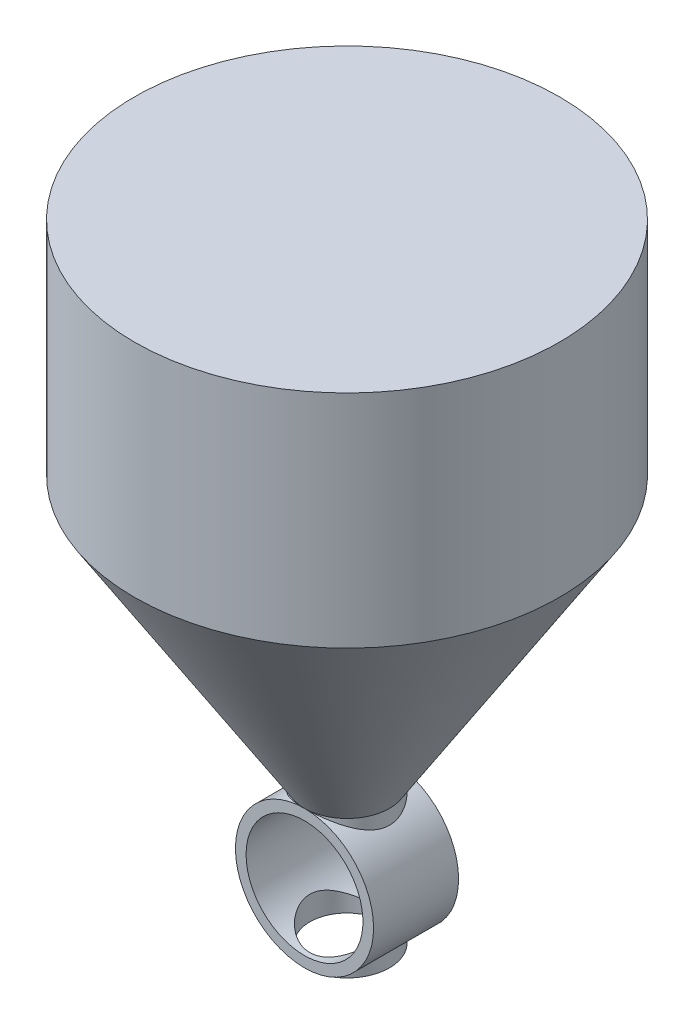
SolidWorks part; units mm, degrees
ref_plane "Alzado" through (0, 0, 0) normal (0, 0, 1) x (1, 0, 0)
ref_plane "Planta" through (0, 0, 0) normal (0, 1, 0) x (1, 0, 0)
ref_plane "Vista lateral" through (0, 0, 0) normal (1, 0, 0) x (0, 0, -1)
sketch "Croquis1" plane through (0, 0, 0) normal (0, 1, 0) x (1, 0, 0)
  circle A0 centre (0, 0) radius 100
  dimension "D1" = 200
ref_plane "Plano1" through (0, -230, 0) normal (0, 1, 0) x (1, 0, 0)
extrude "Saliente-Extruir1" add sketch "Croquis1" against normal blind 104 contours A0
sketch "Croquis2" plane through (0, -104, 0) normal (0, -1, 0) x (1, 0, 0)
  circle A2 centre (0, 0) radius 100
sketch "Croquis3" plane through (0, -230, 0) normal (0, 1, 0) x (1, 0, 0)
  circle A0 centre (0, 0) radius 20
  dimension "D1" = 40
loft "Recubrir1" add profiles "Croquis3", "Croquis2" connector at (-19.9701, -230, 1.0927) connector at (-99.8027, -104, 6.2791)
sketch "Croquis4" plane through (0, -230, 0) normal (0, -1, 0) x (1, 0, 0)
  circle A0 centre (0, 0) radius 20
  dimension "D1" = 40
extrude "Saliente-Extruir2" add sketch "Croquis4" along normal blind 65
ref_plane "Plano2" through (0, 0, -20) normal (0, 0, -1) x (-1, 0, 0)
sketch "Croquis5" plane through (0, 0, -20) normal (0, 0, -1) x (-1, 0, 0)
  line L0 (0, -230) -> (0, -295) construction
  line L1 (110, -230) -> (-110, -230) construction
  line L2 (-32.5, -262.5) -> (32.5, -262.5) construction
  circle A0 centre (0, -262.5) radius 32.5
  point P7 (0, -262.5)
  point P8 (0, -262.5)
  dimension "D1" = 65
  dimension "D2" = 65
extrude "Saliente-Extruir3" add sketch "Croquis5" against normal blind 40
sketch "Croquis6" plane through (0, 0, -20) normal (0, 0, -1) x (-1, 0, 0)
  circle A0 centre (0, -262.5) radius 27.5
  dimension "D1" = 55
extrude "Cortar-Extruir1" cut sketch "Croquis6" against normal through all
sketch "Croquis7" plane through (0, -295, 0) normal (0, -1, 0) x (1, 0, 0)
  circle A0 centre (0, 0) radius 17.5
  dimension "D1" = 35
extrude "Cortar-Extruir2" cut sketch "Croquis7" against normal blind 24
